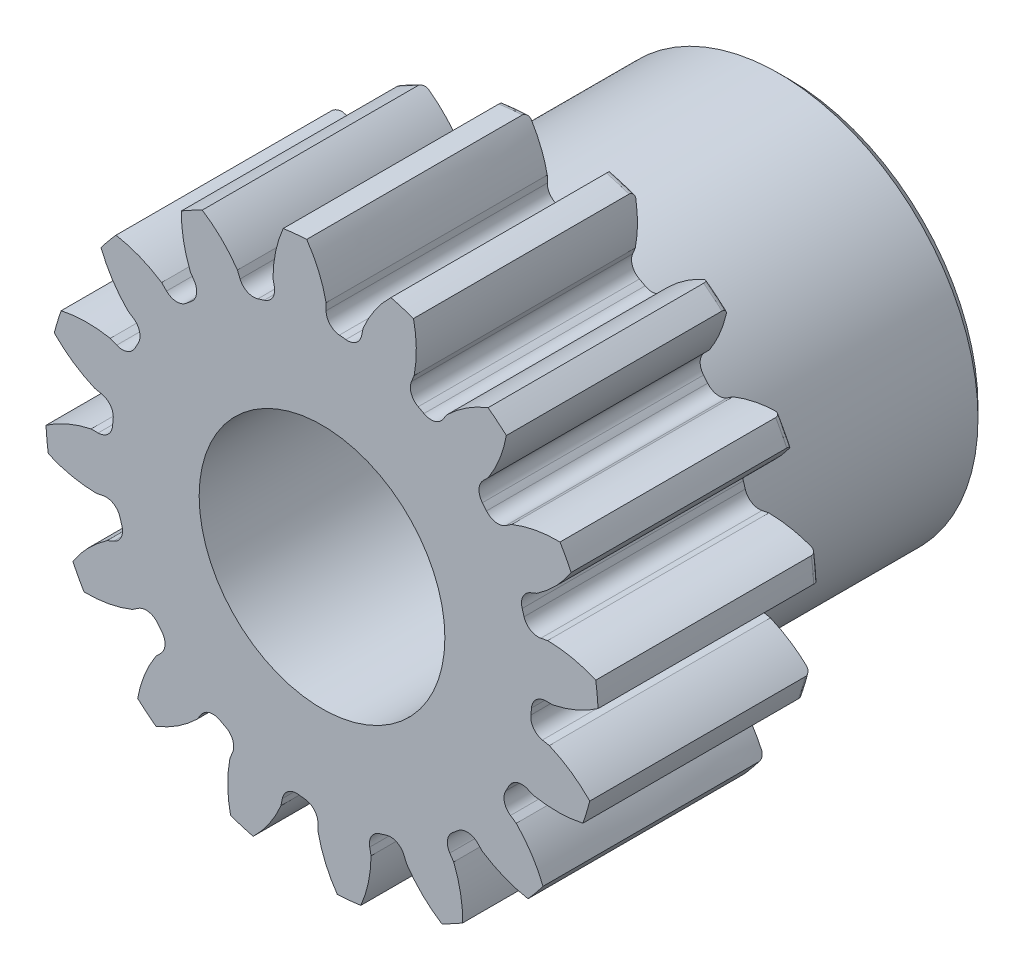
SolidWorks part; units mm, degrees
ref_plane "Front" through (0, 0, 0) normal (0, 0, 1) x (1, 0, 0)
ref_plane "Top" through (0, 0, 0) normal (0, 1, 0) x (1, 0, 0)
ref_plane "Right" through (0, 0, 0) normal (1, 0, 0) x (0, 0, -1)
sketch "Sketch1" plane through (0, 0, 0) normal (0, 0, 1) x (1, 0, 0)
  line L0 (-203.2, 0) -> (203.2, 0) construction
  circle A0 centre (0, 0) radius 14.2875
  circle A1 centre (0, 0) radius 12.7 construction
  circle A3 centre (0, 0) radius 10.8633 construction
  dimension "D1" = 1.8367
  dimension "D2" = 3.4242
  dimension "D3" = 1.5875
extrude "Boss-Extrude1" add sketch "Sketch1" against normal blind 19.05
sketch "Sketch2" plane through (0, 0, 0) normal (1, 0, 0) x (0, 0, -1)
  line L0 (19.05, 0) -> (31.75, 0)
  line L1 (19.05, 0) -> (19.05, 10.287)
  line L2 (19.05, 10.287) -> (31.75, 10.287)
  line L3 (31.75, 10.287) -> (31.75, 0)
  point P5 (31.75, -10.287)
  point P6 (0, -14.2875)
  point P7 (19.05, -14.2875)
  point P9 (0, 14.2875)
revolve "Revolve1" add sketch "Sketch2" angle 360 mid plane about L0
fillet "Fillet2" radius 0.2858 3 edges at (14.2875, 0, -19.05) (14.2875, 0, 0) (10.287, 0, -19.05)
sketch "Sketch3" plane through (0, 0, 0) normal (0, 0, 1) x (1, 0, 0)
  line L0 (0, 0) -> (0, 14.2875) construction
  line L1 (-4.0817, 11.2144) -> (0, 12.7)
  line L2 (-9.5921, 12.7) -> (9.5921, 12.7) construction
  line L3 (-9.0136, 9.4193) -> (9.0136, 15.9807) construction
  line L4 (-4.0817, 11.2144) -> (0, 0) construction
  line L5 (-9.951, 6.5878) -> (0, 0) construction
  line L6 (-9.951, 6.5878) -> (-3.3571, 16.548) construction
  line L7 (-2.8353, 11.5924) -> (0, 0) construction
  line L8 (-2.8353, 11.5924) -> (0.1182, 12.3148) construction
  arc A0 (-4.0817, 11.2144) -> (-9.951, 6.5878) centre (0, 0) ccw
  circle A1 centre (0, 0) radius 12.7 construction
  circle A2 centre (0, 0) radius 11.9341 construction
  arc A3 (-4.0817, 11.2144) -> (-2.8353, 11.5924) centre (0, 0) cw
  circle A4 centre (0, 0) radius 14.2875 construction
  point P6 (0, 12.7)
  dimension "D1" = 4.3437
  dimension "D3" = 11.9451
  dimension "D5" = 3.0406
  dimension "D2" = 7.6014
  dimension "D4" = 1.3031
sketch "Sketch4" plane through (0, 0, 0) normal (0, 0, 1) x (1, 0, 0)
  line L0 (0, 0) -> (1.2388, 12.578) construction
  line L1 (0.2108, 11.9322) -> (0.2108, 10.8612)
  line L2 (0, 12.7) -> (2.4777, 12.456) construction
  line L3 (2.1211, 11.7441) -> (1.9122, 10.6937)
  line L4 (0.2108, 10.8612) -> (0, 0) construction
  line L5 (0, 0) -> (0, 14.2875) construction
  line L6 (-9.951, 6.5878) -> (-3.3571, 16.548) construction
  line L7 (-9.951, 6.5878) -> (-3.3571, 16.548) construction
  arc A0 (1.9122, 10.6937) -> (0.2108, 10.8612) centre (0, 0) ccw
  arc A1 (0, 12.7) -> (2.4777, 12.456) centre (0, 0) cw construction
  circle A2 centre (0, 0) radius 12.7 construction
  circle A3 centre (0, 0) radius 11.9341 construction
  circle A4 centre (0, 0) radius 10.8633 construction
  arc A5 (6.521, 15.5751) -> (-3.3571, 16.548) centre (0, 0) ccw
  spline S0 degree 2 poles (-3.3571, 16.548) (-0.4015, 14.8243) (0.2108, 11.9322) knots 0 0 0 1 1 1
  spline S1 degree 2 poles (6.521, 15.5751) (3.2858, 14.4611) (2.1211, 11.7441) knots 0 0 0 1 1 1
  dimension "D1" = 2.4936
extrude "Cut-Extrude1" cut sketch "Sketch4" against normal through all
fillet "Fillet1" radius 0.7481 2 edges at (1.9122, 10.6937, -9.525) (0.2108, 10.8612, -9.525)
pattern_circular "CirPattern1" count 16 over 360 about axis through (0, 0, -19.05) along (0, 0, 1) of "Cut-Extrude1", "Fillet1"
sketch "Sketch5" plane through (0, 0, 0) normal (0, 0, 1) x (1, 0, 0)
  circle A0 centre (0, 0) radius 6.35
  circle A1 centre (0, 0) radius 6.35 construction
  dimension "Bore Min" = 12.7
  dimension "Bore Max" = 12.7
extrude "Cut-Extrude2" cut sketch "Sketch5" against normal through all
chamfer "Chamfer1" distance 0.5144 angle 45 3 edges at (10.287, 0, -31.75) (6.35, 0, 0) (6.35, 0, -31.75)
sketch "Pitch Dia" plane through (0, 0, 0) normal (0, 0, 1) x (1, 0, 0)
  circle A0 centre (0, 0) radius 12.7 construction
  circle A1 centre (0, 0) radius 12.7 construction
sketch "Sketch6" plane through (0, 0, 0) normal (0, 0, 1) x (1, 0, 0)
  circle A0 centre (0, 0) radius 18.0769
extrude "Cut-Extrude3" cut sketch "Sketch6" against normal blind 7.62
equation "\"D1@Boss-Extrude1\" = \"Face Wd@Sketch2\""
equation "\"D2@Sketch3\" = \"D1@Sketch3\"*1.75"
equation "\"D3@Sketch3\" = \"D1@Sketch3\"+\"D2@Sketch3\""
equation "\"D4@Sketch3\" = \"D1@Sketch3\"*.3"
equation "\"D5@Sketch3\" = \"D1@Sketch3\"-\"D4@Sketch3\""
equation "\"D1@Sketch4\" = 1.5708/(\"Number of Teeth@Sketch1\"/\"Ptich Dia@Sketch1\")"
equation "\"D1@Chamfer1\" = \"B Hub Dia@Sketch2\"*.025"
equation "\"D1@CirPattern1\" = \"Number of Teeth@Sketch1\""
equation "\"D1@Fillet1\" = \"D1@Sketch4\"*.3"
equation "\"D1@Fillet2\" = \"OD@Sketch1\"*.01"
equation "\"D1@Sketch1\" = 1.157/(\"Number of Teeth@Sketch1\"/\"Ptich Dia@Sketch1\")"
